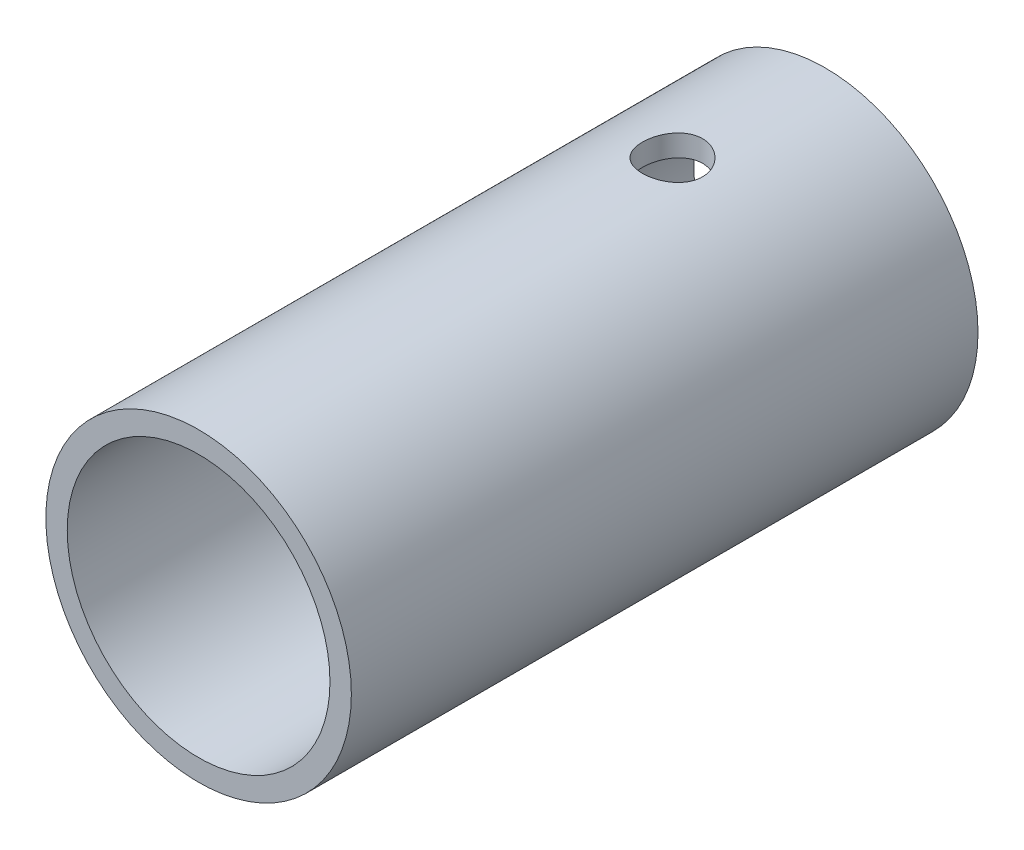
SolidWorks part; units mm, degrees
material "1060 Alloy"
ref_plane "Front" through (0, 0, 0) normal (0, 0, 1) x (1, 0, 0)
ref_plane "Top" through (0, 0, 0) normal (0, 1, 0) x (1, 0, 0)
ref_plane "Right" through (0, 0, 0) normal (1, 0, 0) x (0, 0, -1)
sketch "Sketch1" plane through (0, 0, 0) normal (0, 0, 1) x (1, 0, 0)
  circle A0 centre (0, 0) radius 6.35
  circle A1 centre (0, 0) radius 5.461
extrude "Extrude1" add sketch "Sketch1" along normal blind 26.05 contours A0 A1 region at (-6.1704, 0, 0)
sketch "Sketch2" plane through (0, 0, 0) normal (0, 1, 0) x (1, 0, 0)
  line L0 (0, 0) -> (0, -6.35)
  line L1 (6.35, 0) -> (-6.35, 0) construction
  circle A0 centre (0, -6.35) radius 1.25
  dimension "D1" = 6.35
  dimension "D2" = 2.5
extrude "Cut-Extrude1" cut sketch "Sketch2" against normal blind 38.1 and the other way blind 38.1
